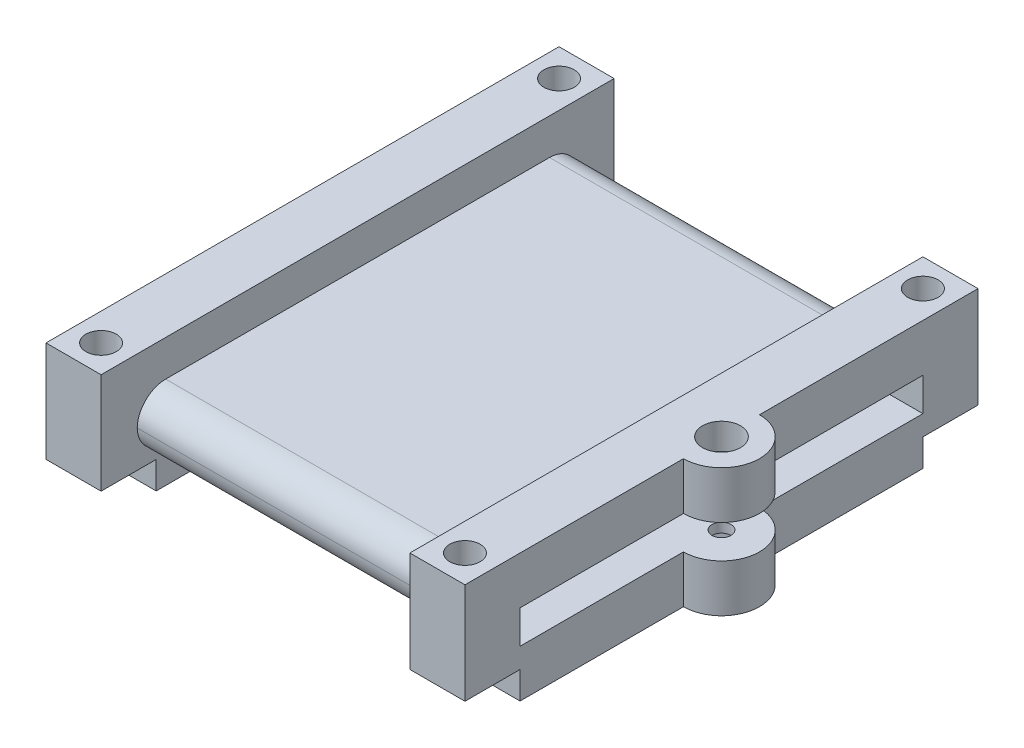
SolidWorks part; units mm, degrees
ref_plane "Front Plane" through (0, 0, 0) normal (0, 0, 1) x (1, 0, 0)
ref_plane "Top Plane" through (0, 0, 0) normal (0, 1, 0) x (1, 0, 0)
ref_plane "Right Plane" through (0, 0, 0) normal (1, 0, 0) x (0, 0, -1)
sketch "Sketch1" plane through (0, 0, 0) normal (1, 0, 0) x (0, 0, -1)
  line L0 (23.2, 5.9) -> (23.2, 0) construction
  line L1 (0, 0) -> (46.4, 0)
  line L2 (0, 0) -> (0, 5.9)
  line L3 (0, 5.9) -> (46.4, 5.9)
  line L4 (46.4, 0) -> (46.4, 5.9)
  line L6 (2, 1.2) -> (44.4, 1.2)
  line L7 (2, 1.2) -> (2, 4.7)
  line L8 (2, 4.7) -> (44.4, 4.7)
  line L9 (44.4, 1.2) -> (44.4, 4.7)
  line L10 (2, 1.2) -> (44.4, 4.7) construction
  line L11 (2, 4.7) -> (44.4, 1.2) construction
  point P7 (23.2, 2.95)
  dimension "D1" = 46.4
  dimension "D2" = 5.9
  dimension "D3" = 3.5
  dimension "D4" = 42.4
extrude "Boss-Extrude1" add sketch "Sketch1" along normal blind 32.5
fillet "Fillet2" radius 3 4 edges at (16.25, 0, -46.4) (16.25, 0, 0) (16.25, 5.9, 0) (16.25, 5.9, -46.4)
sketch "Sketch2" plane through (32.5, 0, 0) normal (1, 0, 0) x (0, 0, -1)
  line L0 (23.2, 5.9) -> (23.2, 0) construction
  line L1 (43.4, 5.9) -> (3, 5.9) construction
  line L2 (3, 0) -> (43.4, 0) construction
  line L4 (-3.8, -3.8) -> (50.2, -3.8)
  line L5 (-3.8, -3.8) -> (-3.8, 9.7)
  line L6 (-3.8, 9.7) -> (50.2, 9.7)
  line L7 (50.2, -3.8) -> (50.2, 9.7)
  line L8 (-3.8, -3.8) -> (50.2, 9.7) construction
  line L9 (-3.8, 9.7) -> (50.2, -3.8) construction
  line L14 (44.4, 1.2) -> (2, 1.2)
  line L15 (44.4, 1.2) -> (44.4, 4.7)
  line L16 (44.4, 4.7) -> (2, 4.7)
  line L17 (2, 1.2) -> (2, 4.7)
  line L18 (44.4, 1.2) -> (2, 4.7) construction
  line L19 (44.4, 4.7) -> (2, 1.2) construction
  point P6 (23.2, 2.95)
  point P11 (23.2, 2.95)
  point P12 (23.2, 2.95)
  dimension "D1" = 13.5
  dimension "D2" = 54
extrude "Boss-Extrude2" add sketch "Sketch2" along normal blind 5.8
sketch "Sketch3" plane through (0, 0, 0) normal (-1, 0, 0) x (0, 0, 1)
  line L0 (-23.2, 5.9) -> (-23.2, 0) construction
  line L1 (-43.4, 5.9) -> (-3, 5.9) construction
  line L2 (-3, 0) -> (-43.4, 0) construction
  line L4 (3.8, -3.8) -> (-50.2, -3.8)
  line L5 (3.8, -3.8) -> (3.8, 9.7)
  line L6 (3.8, 9.7) -> (-50.2, 9.7)
  line L7 (-50.2, -3.8) -> (-50.2, 9.7)
  line L8 (3.8, -3.8) -> (-50.2, 9.7) construction
  line L9 (3.8, 9.7) -> (-50.2, -3.8) construction
  line L10 (-2, 1.2) -> (-44.4, 1.2)
  line L11 (-2, 1.2) -> (-2, 4.7)
  line L12 (-2, 4.7) -> (-44.4, 4.7)
  line L13 (-44.4, 1.2) -> (-44.4, 4.7)
  line L14 (-2, 1.2) -> (-44.4, 4.7) construction
  line L15 (-2, 4.7) -> (-44.4, 1.2) construction
  point P6 (-23.2, 2.95)
  point P12 (-23.2, 2.95)
extrude "Boss-Extrude3" add sketch "Sketch3" along normal blind 5.8
sketch "Sketch4" plane through (0, 9.7, 0) normal (0, 1, 0) x (1, 0, 0)
  line L0 (-2.9, 50.2) -> (-2.9, 47.3) construction
  line L1 (-5.8, 50.2) -> (0, 50.2) construction
  line L2 (35.4, 50.2) -> (35.4, 47.3) construction
  line L3 (38.3, 50.2) -> (32.5, 50.2) construction
  line L4 (-2.9, -3.8) -> (-2.9, -0.9) construction
  line L5 (-5.8, -3.8) -> (0, -3.8) construction
  line L6 (35.4, -3.8) -> (35.4, -0.9) construction
  line L7 (38.3, -3.8) -> (32.5, -3.8) construction
  circle A0 centre (-2.9, 47.3) radius 1.6
  circle A1 centre (35.4, 47.3) radius 1.6
  circle A2 centre (-2.9, -0.9) radius 1.6
  circle A3 centre (35.4, -0.9) radius 1.6
  dimension "D2" = 3.2
  dimension "D4" = 3.2
  dimension "D6" = 3.2
  dimension "D8" = 3.2
  dimension "D1" = 2.9
  dimension "D3" = 2.9
  dimension "D5" = 2.9
  dimension "D7" = 2.9
extrude "Cut-Extrude1" cut sketch "Sketch4" against normal through all
sketch "Sketch6" plane through (38.3, 0, 0) normal (1, 0, 0) x (0, 0, -1)
  line L0 (50.2, -3.8) -> (50.2, 9.7) construction
  line L1 (-3.8, -3.8) -> (50.2, -3.8)
  line L2 (-3.8, -3.8) -> (-3.8, 3.4)
  line L3 (-3.8, 3.4) -> (50.2, 3.4)
  line L4 (50.2, -3.8) -> (50.2, 3.4)
  dimension "D1" = 7.2
extrude "Cut-Extrude2" [suppressed] cut sketch "Sketch6" against normal blind 5.8
sketch "Sketch7" plane through (-5.8, 0, 0) normal (-1, 0, 0) x (0, 0, 1)
  line L0 (3.8, -3.8) -> (3.8, 9.7) construction
  line L1 (-50.2, -3.8) -> (3.8, -3.8)
  line L2 (-50.2, -3.8) -> (-50.2, 3.4)
  line L3 (-50.2, 3.4) -> (3.8, 3.4)
  line L4 (3.8, -3.8) -> (3.8, 3.4)
  dimension "D1" = 7.2
extrude "Cut-Extrude3" [suppressed] cut sketch "Sketch7" against normal blind 5.8
sketch "Sketch8" plane through (0, 9.7, 0) normal (0, 1, 0) x (1, 0, 0)
  line L0 (38.3, 50.2) -> (38.3, -3.8) construction
  circle A0 centre (38.3, 23.2) radius 4
  dimension "D1" = 8
extrude "Boss-Extrude4" add sketch "Sketch8" against normal blind 13.5
hole_wizard "CSK for M2 Flat Head Machine Screw1" positions "Sketch12" profile "Sketch13" countersink size "M2" standard "ANSI Metric" end condition through all
sketch "Sketch12" plane through (0, 9.7, 0) normal (0, 1, 0) x (1, 0, 0)
  point P0 (38.3, 23.2)
sketch "Sketch13" plane through (38.3, 9.7, -23.2) normal (1, 0, 0) x (0, 0, 1)
  line L0 (0, 0) -> (0, 13.5)
  line L1 (0, 13.5) -> (1, 13.5)
  line L2 (1, 13.5) -> (1, 3.75)
  line L3 (1, 3.75) -> (2, 2.75)
  line L4 (2, 2.75) -> (2, 0)
  line L6 (2, 0) -> (0, 0)
  line L7 (-1, 3.75) -> (-2, 2.75) construction
  line L11 (0, -6.35) -> (0, 107.95) construction
  dimension "Thru Hole Dia." = 2
  dimension "Thru Hole Depth" = 13.5
  dimension "C'Sink Dia." = 4
  dimension "C'Sink Angle" = 90
  dimension "Head Clearance" = 2.75
sketch "Sketch14" plane through (0, -3.8, 0) normal (0, -1, 0) x (1, 0, 0)
  line L1 (38.3, -20.7751) -> (36.2, -21.9876)
  line L2 (36.2, -21.9876) -> (36.2, -24.4124)
  line L3 (36.2, -24.4124) -> (38.3, -25.6249)
  line L4 (38.3, -25.6249) -> (40.4, -24.4124)
  line L5 (40.4, -24.4124) -> (40.4, -21.9876)
  line L6 (40.4, -21.9876) -> (38.3, -20.7751)
  circle A0 centre (38.3, -23.2) radius 2.1 construction
  dimension "D1" = 4.2
extrude "Cut-Extrude4" cut sketch "Sketch14" against normal blind 4
sketch "Sketch15" plane through (-5.8, 0, 0) normal (-1, 0, 0) x (0, 0, 1)
  line L1 (-44.4, 1.2) -> (-2, 1.2)
  line L2 (-44.4, 1.2) -> (-44.4, 4.7)
  line L3 (-44.4, 4.7) -> (-2, 4.7)
  line L4 (-2, 1.2) -> (-2, 4.7)
  line L5 (-50.2, -3.8) -> (-44.4, -3.8)
  line L6 (-50.2, -3.8) -> (-50.2, -0.92)
  line L7 (-50.2, -0.92) -> (-44.4, -0.92)
  line L8 (-44.4, -3.8) -> (-44.4, -0.92)
  line L9 (3.8, -3.8) -> (-2, -3.8)
  line L10 (3.8, -3.8) -> (3.8, -0.92)
  line L11 (3.8, -0.92) -> (-2, -0.92)
  line L12 (-2, -3.8) -> (-2, -0.92)
  dimension "D1" = 5.8
  dimension "D2" = 2.88
  dimension "D3" = 5.8
  dimension "D4" = 2.88
extrude "Cut-Extrude5" cut sketch "Sketch15" against normal through all
fillet "Fillet3" radius 2 1 edges at (-5.8, -3.8, -23.2)
